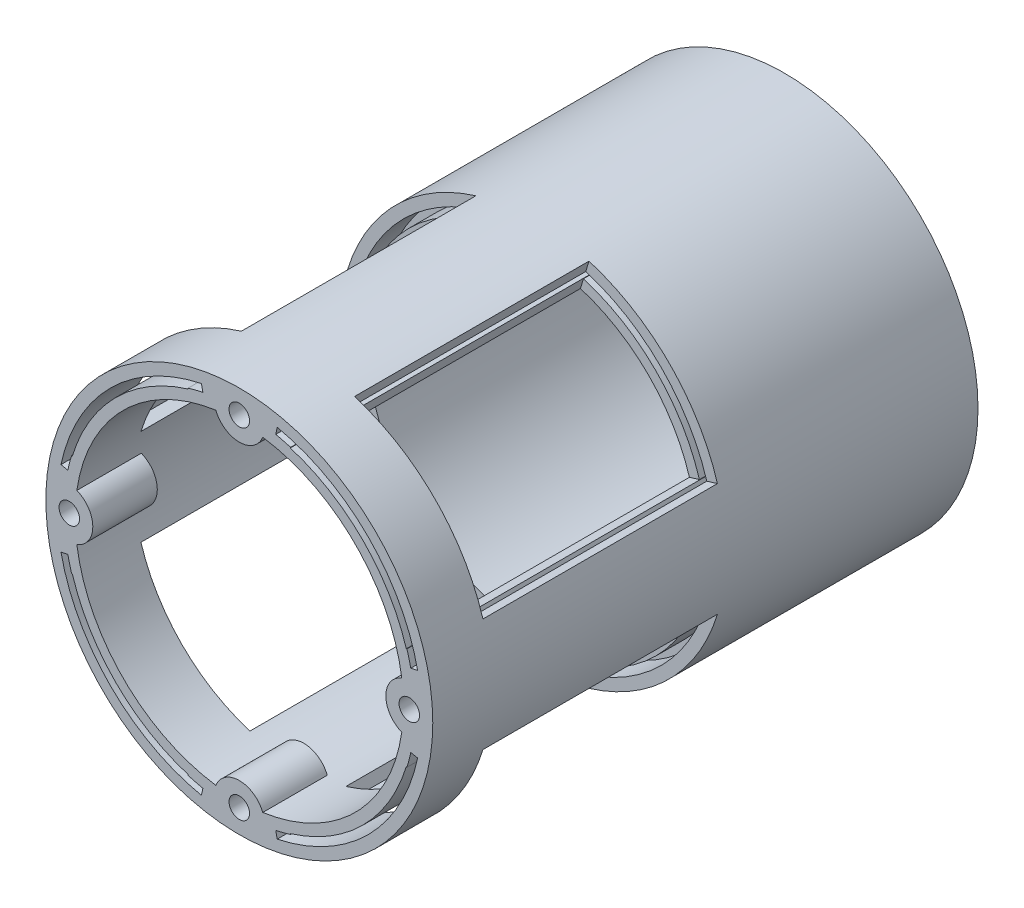
SolidWorks part; units mm, degrees
material "ABS"
ref_plane "Alzado" through (0, 0, 0) normal (0, 0, 1) x (1, 0, 0)
ref_plane "Planta" through (0, 0, 0) normal (0, 1, 0) x (1, 0, 0)
ref_plane "Vista lateral" through (0, 0, 0) normal (1, 0, 0) x (0, 0, -1)
sketch "Croquis1" plane through (0, 0, 0) normal (0, 0, 1) x (1, 0, 0)
  circle A0 centre (0, 0) radius 33
  circle A1 centre (0, 0) radius 28
  dimension "D1" = 66
  dimension "D2" = 5
extrude "Boss-Extrude1" add sketch "Croquis1" along normal blind 93
sketch "Croquis2" plane through (0, 0, 93) normal (0, 0, 1) x (1, 0, 0)
  line L0 (0, 0) -> (-6.4661, -30.4204) construction
  line L1 (0, 0) -> (-30.4204, -6.4661) construction
  line L2 (0, 0) -> (0, -30.5) construction
  line L3 (0, 0) -> (-30.5, 0) construction
  line L4 (-30.4204, -6.4661) -> (-29.2466, -6.2166)
  line L5 (-6.4661, -30.4204) -> (-6.2166, -29.2466)
  line L6 (-30.4204, 6.4661) -> (-29.2466, 6.2166)
  line L7 (-6.4661, 30.4204) -> (-6.2166, 29.2466)
  line L8 (6.4661, 30.4204) -> (6.2166, 29.2466)
  line L9 (30.4204, 6.4661) -> (29.2466, 6.2166)
  line L10 (30.4204, -6.4661) -> (29.2466, -6.2166)
  line L11 (6.4661, -30.4204) -> (6.2166, -29.2466)
  circle A0 centre (0, 0) radius 29.9 construction
  circle A1 centre (0, 0) radius 31.1 construction
  circle A2 centre (0, 0) radius 33 construction
  circle A3 centre (0, 0) radius 30.5 construction
  arc A4 (-6.4661, -30.4204) -> (-30.4204, -6.4661) centre (0, 0) cw
  arc A5 (-6.2166, -29.2466) -> (-29.2466, -6.2166) centre (0, 0) cw
  arc A6 (-30.4204, 6.4661) -> (-6.4661, 30.4204) centre (0, 0) cw
  arc A7 (-29.2466, 6.2166) -> (-6.2166, 29.2466) centre (0, 0) cw
  arc A8 (6.4661, 30.4204) -> (30.4204, 6.4661) centre (0, 0) cw
  arc A9 (6.2166, 29.2466) -> (29.2466, 6.2166) centre (0, 0) cw
  arc A10 (30.4204, -6.4661) -> (6.4661, -30.4204) centre (0, 0) cw
  arc A11 (29.2466, -6.2166) -> (6.2166, -29.2466) centre (0, 0) cw
  circle A12 centre (0, 0) radius 28 construction
  point P4 (-6.3413, -29.8335)
  point P32 (0, 0)
  dimension "D3" = 12
  dimension "D4" = 12
  dimension "D1" = 1.2
  dimension "D2" = 5
  dimension "D6" = 2.5
  dimension "D5" = 4
extrude "Cortar-Extruir1" cut sketch "Croquis2" against normal blind 55
ref_axis "Eje1" through (0, 0, 93) along (0, 0, -1)
ref_plane "Plano2" through (0, 0, 0) normal (0.9563, -0.2924, 0) x (0, 0, -1)
sketch "Croquis4" plane through (0, 0, 0) normal (0.9563, -0.2924, 0) x (0, 0, -1)
  line L0 (-83, 33) -> (-83, 30.9839)
  line L1 (0, 33) -> (-93, 33) construction
  line L2 (-83, 27.7679) -> (-43, 27.7679)
  line L3 (-43, 27.7679) -> (-43, 29.7839)
  line L4 (-43, 33) -> (-83, 33)
  line L5 (-97, 29) -> (-42, 29) construction
  line L6 (-93, 33) -> (-93, -33) construction
  line L7 (-93, 30.9839) -> (-83, 30.9839)
  line L8 (-38, 30.9839) -> (-38, 29.7839)
  line L9 (-38, 29.7839) -> (-43, 29.7839)
  line L10 (-93, 29.7839) -> (-93, 30.9839)
  line L11 (-83, 29.7839) -> (-93, 29.7839)
  line L12 (-83, 29.7839) -> (-83, 27.7679)
  line L13 (-43, 30.9839) -> (-38, 30.9839)
  line L14 (-43, 30.9839) -> (-43, 33)
  line L15 (-93, 30.9817) -> (-93, 29.7862) construction
  point P20 (-93, 30.3839)
  point P21 (-93, 30.3839)
  dimension "D2" = 50
  dimension "D3" = 1.2
  dimension "D5" = 5
  dimension "D6" = 10
revolve "Cortar-Revolución2" cut sketch "Croquis4" angle 56 about axis through (0, 0, 93) along (0, 0, -1)
pattern_circular "MatrizC2" count 4 over 360 about axis through (0, 0, 93) along (0, 0, -1) of "Cortar-Revolución2"
sketch "Sketch8" plane through (0, 0, 0) normal (0, 0, -1) x (-1, 0, 0)
  arc A0 (-4, -27.7128) -> (4, -27.7128) centre (0, 0) ccw
  circle A1 centre (0, 0) radius 28 construction
  arc A2 (-4, -27.7128) -> (4, -27.7128) centre (0, -29.2908) cw
  arc A3 (-27.7128, 4) -> (-27.7128, -4) centre (0, 0) ccw
  arc A4 (-27.7128, 4) -> (-27.7128, -4) centre (-29.2908, 0) cw
  arc A5 (4, 27.7128) -> (-4, 27.7128) centre (0, 0) ccw
  arc A6 (4, 27.7128) -> (-4, 27.7128) centre (0, 29.2908) cw
  arc A7 (27.7128, -4) -> (27.7128, 4) centre (0, 0) ccw
  arc A8 (27.7128, -4) -> (27.7128, 4) centre (29.2908, 0) cw
  point P8 (0, -24.9908)
  point P20 (0, 0)
  dimension "D1" = 4.3
  dimension "D2" = 8
  dimension "D3" = 4
extrude "Boss-Extrude4" add sketch "Sketch8" against normal blind 11
sketch "Sketch9" plane through (0, 0, 0) normal (0, 0, -1) x (-1, 0, 0)
  circle A0 centre (0, -29) radius 1.75
  circle A1 centre (0, 0) radius 29 construction
  circle A2 centre (0, 0) radius 33 construction
  circle A3 centre (-29, 0) radius 1.75
  circle A4 centre (0, 29) radius 1.75
  circle A5 centre (29, 0) radius 1.75
  point P16 (0, 0)
  dimension "D1" = 4
  dimension "D2" = 3.5
  dimension "D3" = 4
extrude "Cut-Extrude3" cut sketch "Sketch9" against normal blind 10
ref_plane "Mid plane" through (0, 0, 46.5) normal (0, 0, 1) x (1, 0, 0)
mirror "Mirror1" about plane through (0, 0, 46.5) normal (0, 0, 1) of "Cut-Extrude3", "Boss-Extrude4"
equation "\"D6@Croquis2\"=\"D2@Croquis2\"/2"
